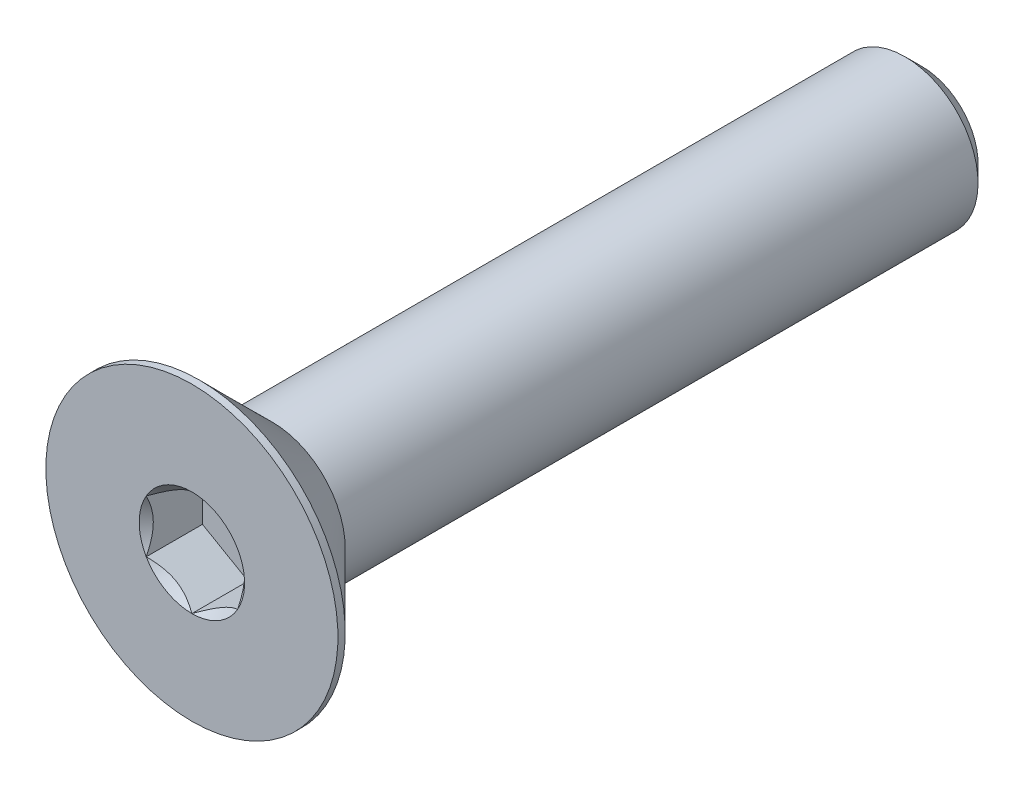
SolidWorks part; units mm, degrees
ref_plane "Front" through (0, 0, 0) normal (0, 0, 1) x (1, 0, 0)
ref_plane "Top" through (0, 0, 0) normal (0, 1, 0) x (1, 0, 0)
ref_plane "Right" through (0, 0, 0) normal (1, 0, 0) x (0, 0, -1)
sketch "Sketch1" plane through (0, 0, 0) normal (1, 0, 0) x (0, 0, -1)
  line L0 (0, 8) -> (0.4, 8) construction
  line L1 (0.4, 8) -> (4.4, 4) construction
  line L2 (0, 4) -> (40, 4)
  line L3 (40, 4) -> (40, 0)
  line L4 (40, 0) -> (0, 0)
  line L5 (0, 0) -> (0, 8) construction
  line L6 (0, 8) -> (0, -8) construction
  line L7 (40, 4) -> (40, -4) construction
  line L8 (0, -8) -> (0.4, -8) construction
  line L9 (0.4, -8) -> (4.4, -4) construction
  line L11 (0, 4) -> (0, 0)
  line L12 (4.4, 4) -> (4.4, 0) construction
revolve "Revolve1" add sketch "Sketch1" angle 360 mid plane about L4
sketch "Sketch3" plane through (0, 0, -40) normal (0, 0, -1) x (-1, 0, 0)
  circle A0 centre (0, 0) radius 4
curve "Helix/Spiral1" pitch 1.25 height 40 turns 32
sketch "Sketch2" plane through (0, 0, 0) normal (1, 0, 0) x (0, 0, -1)
  line L0 (40, 4) -> (41.0938, 4)
  line L1 (41.0938, 4) -> (40.625, 3.1881)
  line L2 (40.625, 3.1881) -> (40.4688, 3.1881)
  line L3 (40.4688, 3.1881) -> (40, 4)
  line L4 (40.2344, 3.5941) -> (40.8594, 3.5941) construction
  dimension "D1" = 60
  dimension "D2" = 0.1562
  dimension "D3" = 0.625
chamfer "Chamfer1" distance 0.9375 angle 45 1 edges at (0, 4, -40)
sweep "Cut-Sweep1" [suppressed] cut profiles "Sketch2" path "Helix/Spiral1"
sketch "Sketch7" plane through (0, 0, 0) normal (1, 0, 0) x (0, 0, -1)
  line L0 (0, 8) -> (0.4, 8) construction
  line L1 (0.4, 8) -> (4.4, 4) construction
  line L2 (0, 8) -> (0.4, 8)
  line L3 (0.4, 8) -> (4.4, 4)
  line L4 (4.4, 4) -> (4.4, 0) construction
  line L5 (4.4, 4) -> (4.4, 0)
  line L7 (0, 0) -> (0, 8) construction
  line L8 (0, 0) -> (0, 8)
  line L9 (0, 0) -> (4.4, 0)
  line L10 (8.8, 0) -> (-8.8, 0) construction
revolve "Revolve2" add sketch "Sketch7" angle 360 mid plane about L9
ref_plane "Plane1" through (0, 0, -4.4) normal (0, 0, 1) x (1, 0, 0)
sketch "Sketch8" plane through (0, 0, -4.4) normal (0, 0, 1) x (1, 0, 0)
  circle A0 centre (0, 0) radius 4
extrude "Boss-Extrude1" add sketch "Sketch8" against normal through all draft 45
sketch "Sketch5" plane through (0, 0, 0) normal (0, 0, 1) x (1, 0, 0)
  line L1 (2.5, -1.4434) -> (2.5, 1.4434)
  line L2 (2.5, 1.4434) -> (0, 2.8868)
  line L3 (0, 2.8868) -> (-2.5, 1.4434)
  line L4 (-2.5, 1.4434) -> (-2.5, -1.4434)
  line L5 (-2.5, -1.4434) -> (0, -2.8868)
  line L6 (0, -2.8868) -> (2.5, -1.4434)
  circle A0 centre (0, 0) radius 2.5 construction
  dimension "Hex" = 5
extrude "Cut-Extrude2" cut sketch "Sketch5" against normal blind 3.08
sketch "Sketch6" plane through (0, 0, 0) normal (0, 0, 1) x (1, 0, 0)
  circle A0 centre (0, 0) radius 2.8868
extrude "Cut-Extrude3" cut sketch "Sketch6" against normal blind 3.08 draft 45
sketch "Sketch9" [suppressed] plane through (0, 0, -1.5) normal (0, 0, 1) x (1, 0, 0)
  circle A1 centre (0, 0) radius 1.25
  circle A2 centre (0, 0) radius 1.25
  point P0 (0, 1.25)
  dimension "D1" = 0
extrude "Boss-Extrude2" [suppressed] add sketch "Sketch9" against normal offset from surface (3.5 mm away) 26
fillet "Fillet1" [suppressed] radius 0.8
sketch "Sketch10" plane through (0, 0, 0) normal (1, 0, 0) x (0, 0, -1)
  line L0 (40, 4) -> (40, -4) construction
  point P0 (38.125, -4)
  dimension "D1" = 1.875
move or copy body "Body-Move/Copy1" [suppressed] bodies to move or copy 113
equation "\"D3@Helix/Spiral1\" = \"Lg@Sketch1\""
equation "\"D2@Sketch2\" = \"D4@Helix/Spiral1\" * .125"
equation "\"D3@Sketch2\" = \"D4@Helix/Spiral1\" * .5"
equation "\"D1@Chamfer1\" = \"D4@Helix/Spiral1\" * .75"
equation "\"D1@Cut-Extrude2\" = \"Head Ht@Sketch1\" * .7"
equation "\"D1@Sketch10\" = \"D4@Helix/Spiral1\" * 1.5"
equation "\"D1@Cut-Extrude3\" = \"D1@Cut-Extrude2\""
equation "\"D1@Fillet1\" = \"Dia@Sketch1\" * .1"
